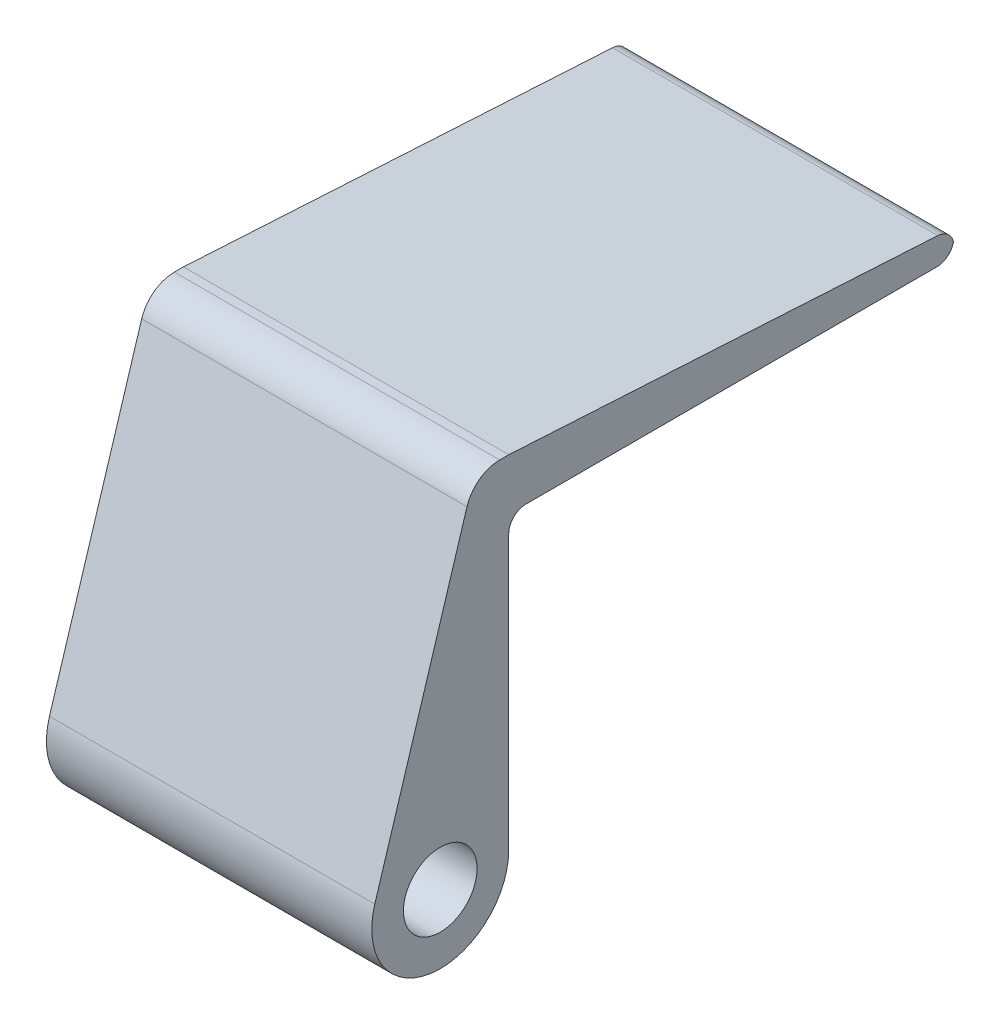
SolidWorks part; units mm, degrees
ref_plane "Front Plane" through (0, 0, 0) normal (0, 0, 1) x (1, 0, 0)
ref_plane "Top Plane" through (0, 0, 0) normal (0, 1, 0) x (1, 0, 0)
ref_plane "Right Plane" through (0, 0, 0) normal (1, 0, 0) x (0, 0, -1)
sketch "Sketch1" plane through (0, 0, 0) normal (1, 0, 0) x (0, 0, -1)
  line L22 (4, 10) -> (4, 0)
  line L26 (4, 10) -> (4, 17)
  line L28 (30, 18.5) -> (30, 17)
  line L29 (2, 20) -> (4, 20)
  line L30 (2, 20) -> (-3.8213, 1.1821)
  line L31 (30, 17) -> (4, 17)
  line L32 (4, 20) -> (30, 18.5)
  circle A5 centre (0, 0) radius 2.15
  arc A7 (-3.8213, 1.1821) -> (4, 0) centre (0, 0) ccw
extrude "Boss-Extrude1" add sketch "Sketch1" along normal mid plane 19
fillet "Fillet1" radius 2 1 edges at (0, 20, -2)
fillet "Fillet2" radius 1 3 edges at (0, 17, -30) (0, 18.5, -30) (0, 17, -4)
